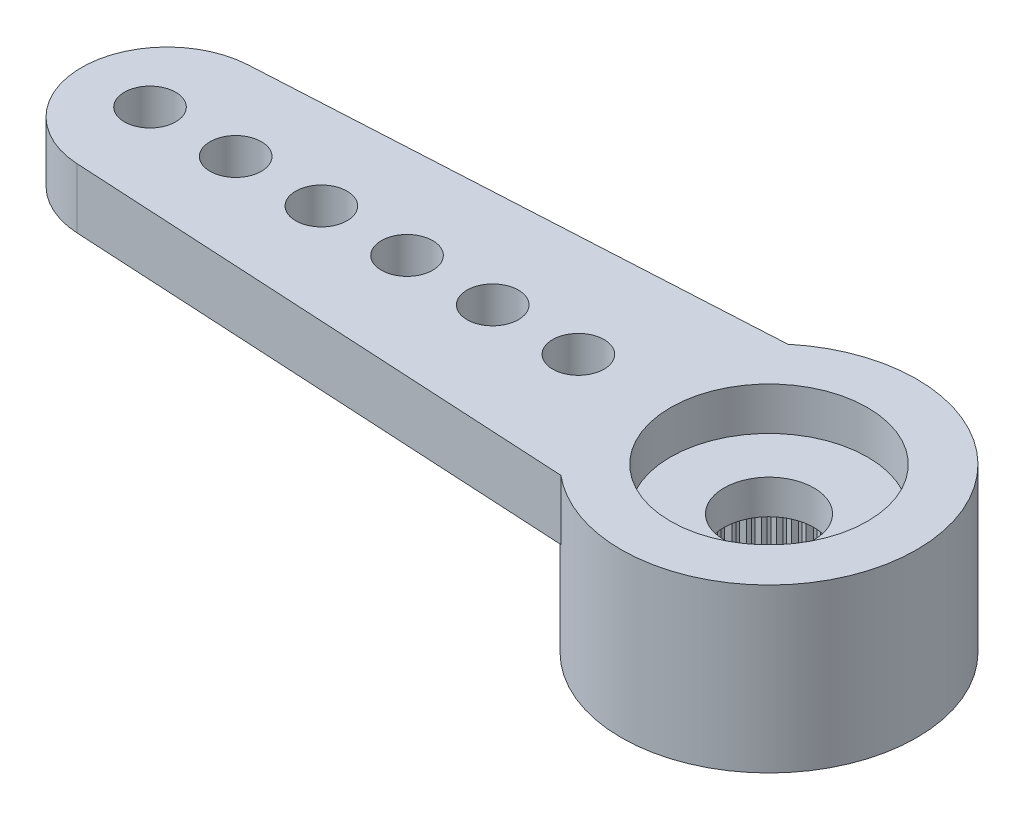
SolidWorks part; units mm, degrees
material "PVC Rígido"
ref_plane "Plano frontal" through (0, 0, 0) normal (0, 0, 1) x (1, 0, 0)
ref_plane "Plano superior" through (0, 0, 0) normal (0, 1, 0) x (1, 0, 0)
ref_plane "Plano direito" through (0, 0, 0) normal (1, 0, 0) x (0, 0, -1)
sketch "Esboço1" plane through (0, 0, 0) normal (0, 1, 0) x (1, 0, 0)
  line L0 (0, 0) -> (-14.05, 0) construction
  line L1 (-14.1591, 1.997) -> (-2.2091, 2.65)
  line L2 (-2.2091, -2.65) -> (-14.1591, -1.997)
  arc A0 (-2.2091, -2.65) -> (-2.2091, 2.65) centre (0, 0) ccw
  arc A1 (-14.1591, 1.997) -> (-14.1591, -1.997) centre (-14.05, 0) ccw
  dimension "D1" = 6.9
  dimension "D2" = 4
  dimension "D3" = 19.5
  dimension "D4" = 5.3
extrude "Ressalto-extrusão1" add sketch "Esboço1" against normal blind 1.4
sketch "Esboço2" plane through (0, -1.4, 0) normal (0, -1, 0) x (1, 0, 0)
  arc A0 (-2.2091, -2.65) -> (-2.2091, 2.65) centre (0, 0) ccw construction
  circle A1 centre (0, 0) radius 3.45
extrude "Ressalto-extrusão2" add sketch "Esboço2" along normal offset from surface (2.4 mm away) 3.8 up to face at (-7.242, 0, 0)
hole_wizard "Furo4" positions "Esboço9" profile "Esboço10" legacy end condition through all
sketch "Esboço9" plane through (0, 0, 0) normal (0, 1, 0) x (1, 0, 0)
  line L1 (-14.45, 0) -> (0, 0) construction
  arc A2 (-14.1591, 1.997) -> (-14.1591, -1.997) centre (-14.05, 0) ccw construction
  point P0 (-14.45, 0)
  point P19 (-16.05, 0)
  dimension "D1" = 1.6
sketch "Esboço10" plane through (-14.45, 0, 0) normal (1, 0, 0) x (0, 0, 1)
  line L0 (0, 0) -> (0, 3.8)
  line L1 (0, 3.8) -> (0.6, 3.8)
  line L2 (0.6, 3.8) -> (0.6, 0)
  line L3 (0.6, 0) -> (0, 0)
  line L4 (0, 110) -> (0, -10) construction
  dimension "Diameter" = 1.2
  dimension "Depth" = 3.8
pattern_linear "Padrão linear1" count 6 spacing 2 along (1, 0, 0) of "Furo4"
hole_wizard "Furo1" positions "Esboço3" profile "Esboço4" legacy
sketch "Esboço3" plane through (0, -3.8, 0) normal (0, -1, 0) x (-1, 0, 0)
  point P0 (0, 0)
sketch "Esboço4" plane through (0, -3.8, 0) normal (1, 0, 0) x (0, 0, -1)
  line L0 (0, 0) -> (0, 2)
  line L1 (0, 2) -> (2.475, 2)
  line L2 (2.475, 2) -> (2.475, 0)
  line L3 (2.475, 0) -> (0, 0)
  line L4 (0, 110) -> (0, -10) construction
  dimension "Diameter" = 4.95
  dimension "Depth" = 2
hole_wizard "Furo2" positions "Esboço5" profile "Esboço6" legacy
sketch "Esboço5" plane through (0, 0, 0) normal (0, 1, 0) x (1, 0, 0)
  point P0 (0, 0)
sketch "Esboço6" plane through (0, 0, 0) normal (1, 0, 0) x (0, 0, 1)
  line L0 (0, 0) -> (0, 1)
  line L1 (0, 1) -> (2.3, 1)
  line L2 (2.3, 1) -> (2.3, 0)
  line L3 (2.3, 0) -> (0, 0)
  line L4 (0, 110) -> (0, -10) construction
  dimension "Diameter" = 4.6
  dimension "Depth" = 1
hole_wizard "Furo3" positions "Esboço7" profile "Esboço8" legacy end condition through all
sketch "Esboço7" plane through (0, 0, 0) normal (0, 1, 0) x (1, 0, 0)
  point P0 (0, 0)
sketch "Esboço8" plane through (0, 0, 0) normal (1, 0, 0) x (0, 0, 1)
  line L0 (0, 0) -> (0, 3.8)
  line L1 (0, 3.8) -> (1.05, 3.8)
  line L2 (1.05, 3.8) -> (1.05, 0)
  line L3 (1.05, 0) -> (0, 0)
  line L4 (0, 110) -> (0, -10) construction
  dimension "Diameter" = 2.1
  dimension "Depth" = 3.8
sketch "Esboço11" plane through (0, -3.8, 0) normal (0, -1, 0) x (1, 0, 0)
  line L0 (-0.0981, 2.4731) -> (0, 2.375)
  line L1 (0, 2.375) -> (0.0981, 2.4731)
  line L2 (0, 0) -> (0, 2.475) construction
  circle A0 centre (0, 0) radius 2.375 construction
  circle A1 centre (0, 0) radius 2.475
  arc A2 (0.0981, 2.4731) -> (-0.0981, 2.4731) centre (0, 0) ccw
  dimension "D3" = 4.75
  dimension "D2" = 0.1
  dimension "D1" = 0
extrude "Ressalto-extrusão3" add sketch "Esboço11" against normal up to surface (2 mm away) up to face at (0, -1.8, 1.05)
pattern_circular "PadrãoCircular1" count 60 over 360 about axis through (0, -1.4, 0) along (0, 1, 0) of "Ressalto-extrusão3"
sketch "Sketch1" plane through (0, 0, 0) normal (0, 1, 0) x (1, 0, 0)
  line L0 (0, 0) -> (-14.45, 0) construction
